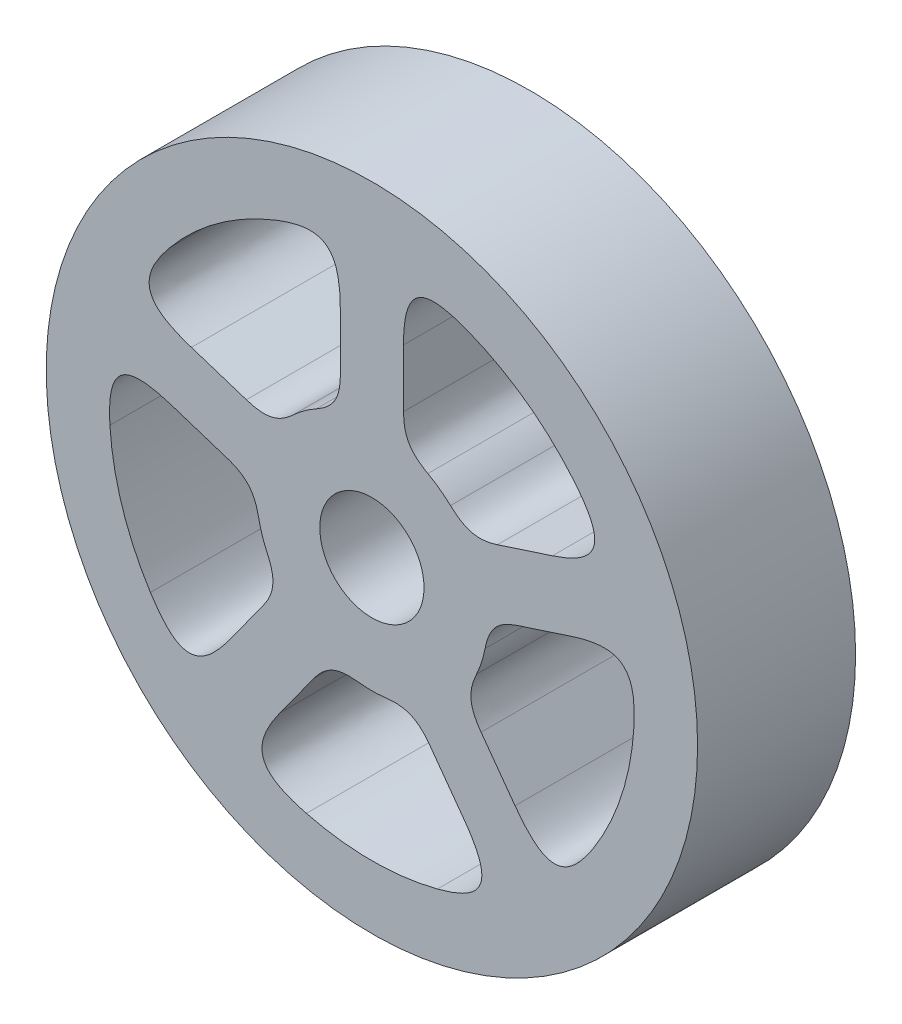
SolidWorks part; units mm, degrees
ref_plane "Front Plane" through (0, 0, 0) normal (0, 0, 1) x (1, 0, 0)
ref_plane "Top Plane" through (0, 0, 0) normal (0, 1, 0) x (1, 0, 0)
ref_plane "Right Plane" through (0, 0, 0) normal (1, 0, 0) x (0, 0, -1)
sketch "Sketch1" plane through (0, 0, 0) normal (0, 0, 1) x (1, 0, 0)
  line L0 (0, 4.6355) -> (0, 10.5489) construction
  line L1 (1.27, 4.4581) -> (1.27, 10.4722)
  line L2 (-1.27, 4.4581) -> (-1.27, 10.4722)
  line L3 (-1.27, 4.6355) -> (-1.27, 10.5489) construction
  line L4 (1.27, 4.6355) -> (1.27, 10.5489) construction
  line L5 (3.8475, 2.5855) -> (9.5672, 4.4439)
  line L6 (4.6324, 0.1698) -> (10.3521, 2.0282)
  line L7 (4.4086, 1.4324) -> (10.0326, 3.2598) construction
  line L8 (3.6479, -2.8602) -> (7.1828, -7.7257)
  line L9 (1.593, -4.3532) -> (5.1279, -9.2187)
  line L10 (2.7247, -3.7502) -> (6.2005, -8.5342) construction
  line L11 (-1.593, -4.3532) -> (-5.1279, -9.2187)
  line L12 (-3.6479, -2.8602) -> (-7.1828, -7.7257)
  line L13 (-2.7247, -3.7502) -> (-6.2005, -8.5342) construction
  line L14 (-4.6324, 0.1698) -> (-10.3521, 2.0282)
  line L15 (-3.8475, 2.5855) -> (-9.5672, 4.4439)
  line L16 (-4.4086, 1.4324) -> (-10.0326, 3.2598) construction
  circle A0 centre (0, 0) radius 2.0955
  circle A1 centre (0, 0) radius 13.0889
  arc A2 (-1.27, 4.4581) -> (-3.8475, 2.5855) centre (0, 0) ccw
  arc A3 (-1.27, 10.4722) -> (-9.5672, 4.4439) centre (0, 0) ccw
  circle A4 centre (0, 0) radius 4.6355 construction
  circle A5 centre (0, 0) radius 10.5489 construction
  arc A6 (-4.6324, 0.1698) -> (-3.6479, -2.8602) centre (0, 0) ccw
  arc A7 (-1.593, -4.3532) -> (1.593, -4.3532) centre (0, 0) ccw
  arc A8 (3.6479, -2.8602) -> (4.6324, 0.1698) centre (0, 0) ccw
  arc A9 (3.8475, 2.5855) -> (1.27, 4.4581) centre (0, 0) ccw
  arc A10 (-10.3521, 2.0282) -> (-7.1828, -7.7257) centre (0, 0) ccw
  arc A11 (-5.1279, -9.2187) -> (5.1279, -9.2187) centre (0, 0) ccw
  arc A12 (7.1828, -7.7257) -> (10.3521, 2.0282) centre (0, 0) ccw
  arc A13 (9.5672, 4.4439) -> (1.27, 10.4722) centre (0, 0) ccw
  point P45 (0, 0)
  dimension "D1" = 4.191
  dimension "D2" = 26.1778
  dimension "D3" = 2.54
  dimension "D4" = 2.54
  dimension "D5" = 1.27
  dimension "D6" = 1.27
  dimension "D7" = 5
extrude "Boss-Extrude1" add sketch "Sketch1" along normal blind 6.35
fillet "Fillet1" radius 1.905 20 edges at (-3.6479, -2.8602, 3.175) (-4.6324, 0.1698, 3.175) (-10.3521, 2.0282, 3.175) (-7.1828, -7.7257, 3.175) (1.593, -4.3532, 3.175) (-1.593, -4.3532, 3.175) (-5.1279, -9.2187, 3.175) (5.1279, -9.2187, 3.175) (-1.27, 10.4722, 3.175) (-3.8475, 2.5855, 3.175) (-1.27, 4.4581, 3.175) (4.6324, 0.1698, 3.175) (3.6479, -2.8602, 3.175) (7.1828, -7.7257, 3.175) (10.3521, 2.0282, 3.175) (1.27, 4.4581, 3.175) (3.8475, 2.5855, 3.175) (9.5672, 4.4439, 3.175) (1.27, 10.4722, 3.175) (-9.5672, 4.4439, 3.175) conic rho 0.55
